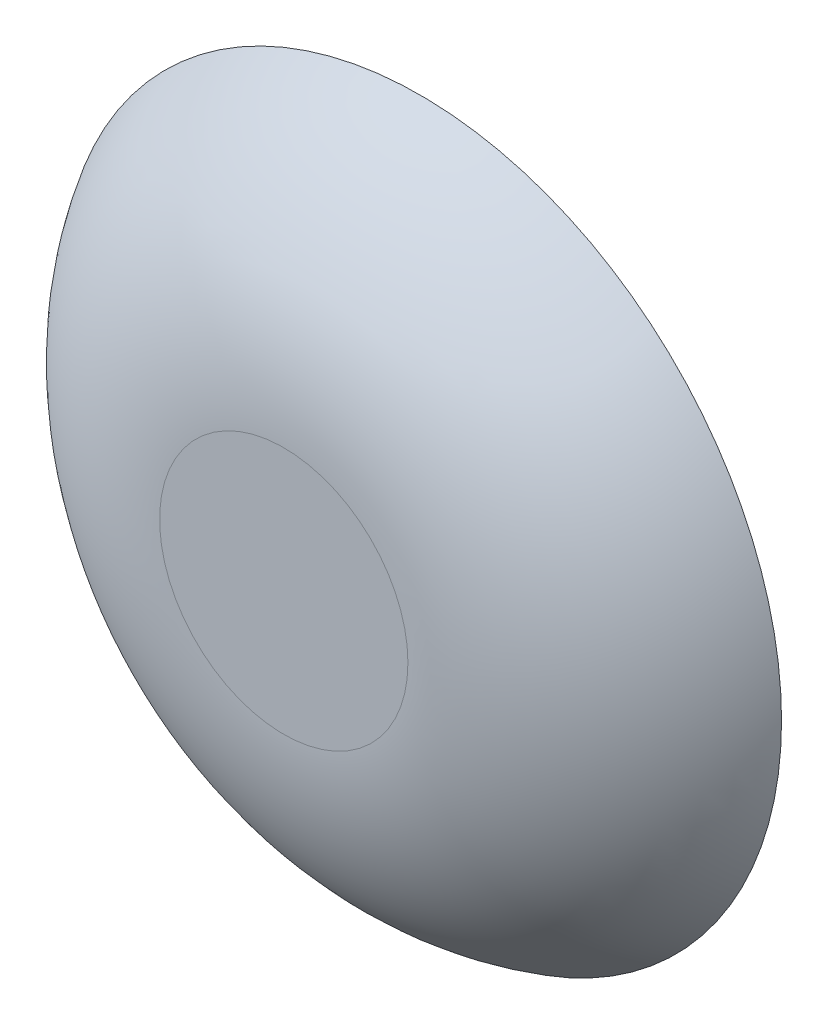
SolidWorks part; units mm, degrees
ref_plane "Front" through (0, 0, 0) normal (0, 0, 1) x (1, 0, 0)
ref_plane "Top" through (0, 0, 0) normal (0, 1, 0) x (1, 0, 0)
ref_plane "Right" through (0, 0, 0) normal (1, 0, 0) x (0, 0, -1)
sketch "Sketch4" plane through (0, 0, 0) normal (0, 0, 1) x (1, 0, 0)
  circle A1 centre (0, 0) radius 33
  dimension "D1" = 66
extrude "Boss-Extrude1" add sketch "Sketch4" along normal blind 12.5
fillet "Fillet1" radius 25 1 edges at (33, 0, 12.5)
shell "Shell3" thickness 2.54 removed face at (33, 0, 0)
